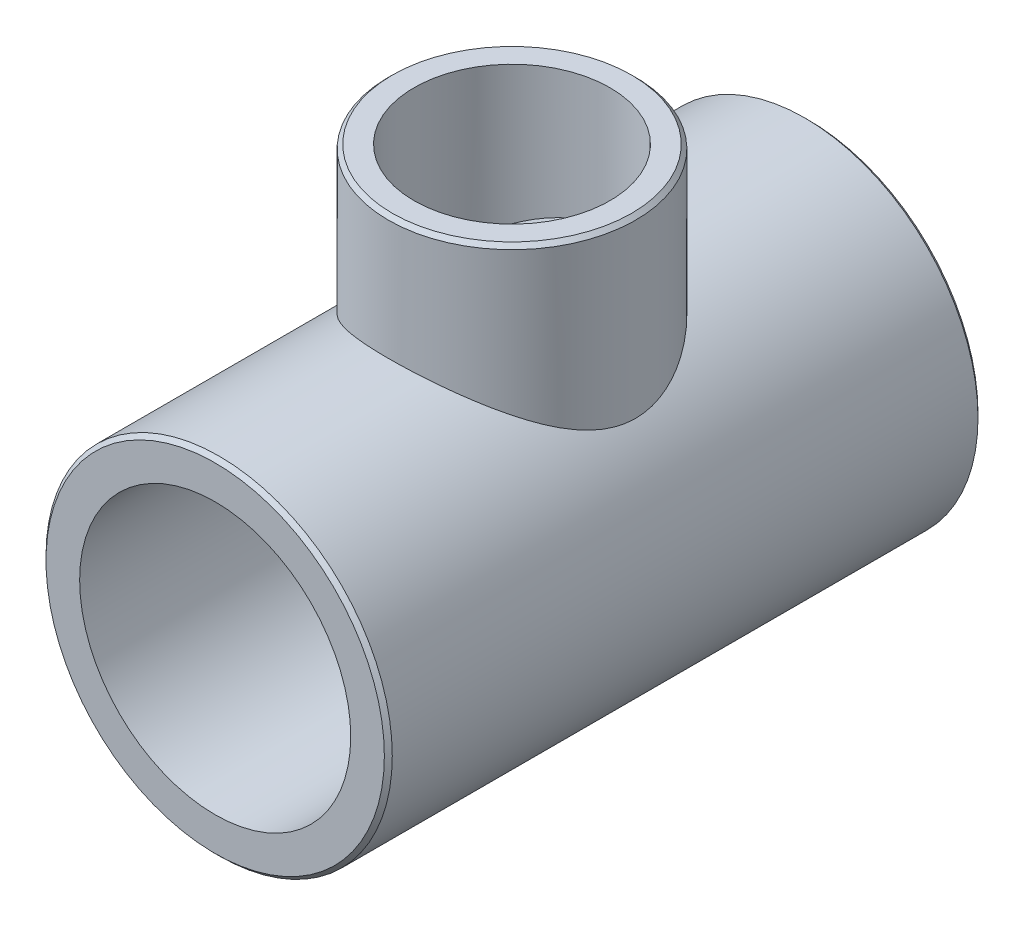
SolidWorks part; units mm, degrees
ref_plane "Front Plane" through (0, 0, 0) normal (0, 0, 1) x (1, 0, 0)
ref_plane "Top Plane" through (0, 0, 0) normal (0, 1, 0) x (1, 0, 0)
ref_plane "Right Plane" through (0, 0, 0) normal (1, 0, 0) x (0, 0, -1)
sketch "OutletRoute" plane through (0, 0, 0) normal (0, 1, 0) x (1, 0, 0)
  circle A0 centre (0, 0) radius 7.9375
  circle A1 centre (0, 0) radius 6.2865
  dimension "Diameter" = 15.875
  dimension "WallThcikness" = 1.651
sketch "RunRoute" plane through (0, 0, 0) normal (0, 0, 1) x (1, 0, 0)
  line L0 (7.9375, 0) -> (-7.9375, 0) construction
  circle A0 centre (0, 0) radius 11.1125
  circle A1 centre (0, 0) radius 8.6995
  dimension "Diameter" = 22.225
  dimension "WallThickness" = 2.413
sketch "Sketch3" plane through (0, 0, 0) normal (1, 0, 0) x (0, 0, -1)
  line L0 (19.05, 0) -> (-19.05, 0) construction
  line L2 (0, 0) -> (0, 19.05) construction
  line L3 (0, 11.1125) -> (0, -11.1125) construction
  point P4 (0, 0)
  dimension "D1" = 38.1
  dimension "D2" = 19.05
extrude "RunExtrude" add sketch "RunRoute" along normal up to vertex (19.05 mm away) and the other way up to vertex (19.05 mm away) contours A0 A1 region at (-10.7982, 0, 0) up to point (0, 0, 19.05) other way up to point (0, 0, -19.05)
extrude "Boss-Extrude2" add sketch "OutletRoute" against normal up to surface (7.9375 mm away) from vertex contours A0 A1 region at (-7.713, 0, 0) up to face at (11.1125, 0, 19.05) starting at point (0, 19.05, 0)
other "CPoint1" parameters "Diameter"=22.225, "StubLength"=0
ref_axis "Axis1" through (0, 0, 29.05) along (0, 0, -1)
other "CPoint2" parameters "Diameter"=22.225, "StubLength"=0
ref_axis "Axis2" through (0, 0, -29.05) along (0, 0, 1)
other "CPoint3" parameters "Diameter"=15.875, "StubLength"=0
ref_axis "Axis3" through (0, 29.05, 0) along (0, -1, 0)
other "RPoint1"
chamfer "Chamfer1" distance 0.254 angle 45 3 edges at (11.1125, 0, 19.05) (11.1125, 0, -19.05) (0, 19.05, 7.9375)
